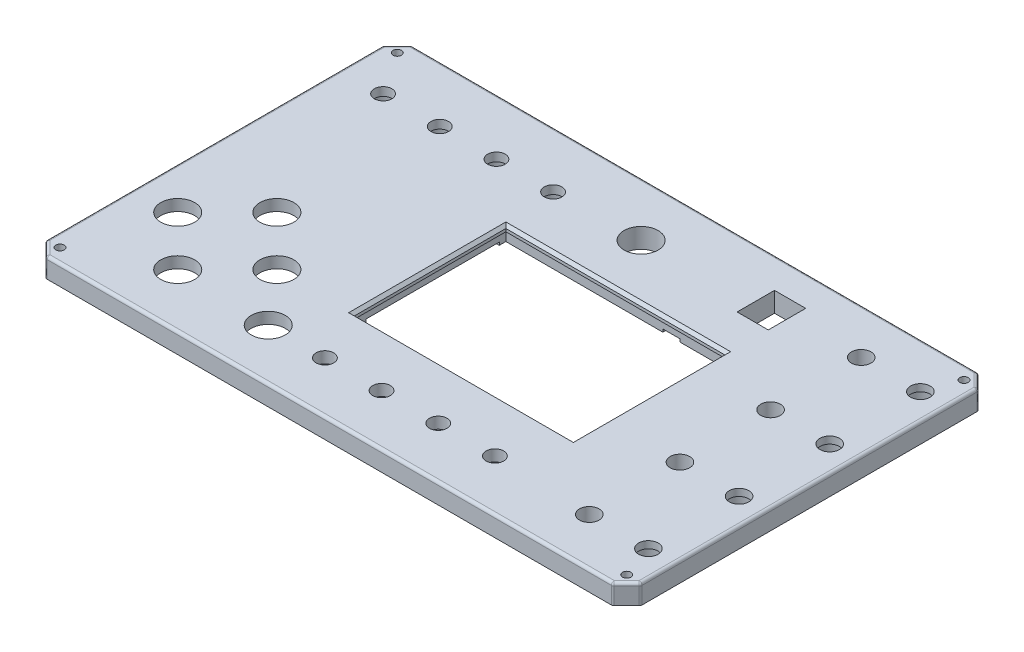
SolidWorks part; units mm, degrees
ref_plane "Front Plane" through (0, 0, 0) normal (0, 0, 1) x (1, 0, 0)
ref_plane "Top Plane" through (0, 0, 0) normal (0, 1, 0) x (1, 0, 0)
ref_plane "Right Plane" through (0, 0, 0) normal (1, 0, 0) x (0, 0, -1)
sketch "Sketch1" plane through (0, 0, 0) normal (0, 1, 0) x (1, 0, 0)
  line L1 (52.5, -34.5) -> (-52.5, -34.5)
  line L2 (52.5, -34.5) -> (52.5, 34.5)
  line L3 (52.5, 34.5) -> (-52.5, 34.5)
  line L4 (-52.5, -34.5) -> (-52.5, 34.5)
  line L5 (52.5, -34.5) -> (-52.5, 34.5) construction
  line L6 (52.5, 34.5) -> (-52.5, -34.5) construction
  point P0 (0, 0)
  dimension "D1" = 105
  dimension "D2" = 69
extrude "Boss-Extrude1" add sketch "Sketch1" along normal blind 5
extrude "Cut-Extrude1" cut sketch "Sketch2" against normal through all
sketch "Sketch2" plane through (17.0721, 0, 5.1034) normal (0, -1, 0) x (-1, 0, 0)
  line L0 (59.7281, 33.0909) -> (-27.1079, 33.0909)
  line L1 (-27.1079, 33.0909) -> (-27.1079, -24.4081)
  line L2 (-27.1079, -24.4081) -> (59.7281, -24.4081)
  line L3 (59.7281, -24.4081) -> (59.7281, 33.0909)
  line L8 (-26.1079, -23.4081) -> (58.7281, -23.4081) construction
  line L9 (-26.1079, 32.0909) -> (-26.1079, -23.4081) construction
  line L10 (58.7281, 32.0909) -> (-26.1079, 32.0909) construction
  line L11 (58.7281, -23.4081) -> (58.7281, 32.0909) construction
extrude "Cut-Extrude2" cut sketch "Sketch3" against normal blind 1
sketch "Sketch3" plane through (17.0721, 0, 5.1034) normal (0, -1, 0) x (-1, 0, 0)
  line L1 (59.8221, 30.7659) -> (54.5248, 30.7659)
  line L2 (59.8221, 30.7659) -> (59.8221, -16.2341) construction
  line L3 (59.8221, -16.2341) -> (54.5248, -16.2341)
  line L8 (65.3221, 30.2659) -> (60.3221, 30.2659) construction
  line L9 (60.3221, 30.2659) -> (60.3221, -15.7341) construction
  line L10 (60.3221, -15.7341) -> (65.3221, -15.7341) construction
  line L11 (65.3221, -15.7341) -> (65.3221, 30.2659) construction
  line L12 (54.5248, 30.7659) -> (54.5248, -16.2341)
  line L20 (65.8221, 30.7659) -> (59.8221, 30.7659)
  line L21 (59.8221, 30.7659) -> (59.8221, -16.2341) construction
  line L22 (59.8221, -16.2341) -> (65.8221, -16.2341)
  line L23 (65.8221, -16.2341) -> (65.8221, 30.7659)
extrude "Cut-Extrude3" cut sketch "Sketch4" against normal blind 1 contours L31 L28 L29 L17 L16 L19 | L19 L16 L17 | L30 L31 L19 L18 L17 L29 | L18 L19 L17 region at (15.76, 0, -28.9025) region at (12.8295, 0, -28.9025)
sketch "Sketch4" plane through (17.0721, 0, 5.1034) normal (0, -1, 0) x (-1, 0, 0)
  line L8 (69.5721, -29.3966) -> (69.5721, 69.6034)
  line L10 (-35.4279, 69.6034) -> (-35.4279, -29.3966)
  line L11 (-35.4279, -29.3966) -> (69.5721, -29.3966)
  line L16 (3.8121, 35.2559) -> (-1.1879, 35.2559)
  line L17 (-1.1879, 35.2559) -> (-1.1879, 32.7559)
  line L18 (-1.1879, 32.7559) -> (3.8121, 32.7559)
  line L19 (3.8121, 32.7559) -> (3.8121, 35.2559)
  line L20 (69.5721, 69.6034) -> (-35.4279, 69.6034)
  line L28 (4.3121, 35.7559) -> (-1.6879, 35.7559)
  line L29 (-1.6879, 35.7559) -> (-1.6879, 32.2559)
  line L30 (-1.6879, 32.2559) -> (4.3121, 32.2559)
  line L31 (4.3121, 32.2559) -> (4.3121, 35.7559)
extrude "Cut-Extrude4" cut sketch "Sketch5" against normal through all contours L3 L2 A3 L5 A2 L4 | L2 L3 L4 A4 L6 A5 region at (42.0883, 0, 0.4104)
sketch "Sketch5" plane through (17.0721, 0, 5.1034) normal (0, -1, 0) x (-1, 0, 0)
  line L2 (-27.1779, 33.1034) -> (-27.1779, 13.8376)
  line L3 (-27.1779, 5.1034) -> (-31.6779, 5.1034) construction
  line L4 (-31.6779, -0.8966) -> (-31.6779, 11.1034)
  line L5 (-30.1159, 12.6653) -> (-28.3501, 12.6653)
  line L6 (-29.4785, -3.0961) -> (-28.6478, -3.0961)
  line L7 (-27.1779, 5.1034) -> (-27.1779, 13.8376) construction
  line L8 (-27.1779, -4.566) -> (-18.8659, -4.566)
  line L9 (-27.1779, -4.566) -> (-27.1779, 5.1034)
  line L10 (-27.1779, 13.8376) -> (-18.8659, 13.8376)
  line L11 (-18.8659, -4.566) -> (-18.8659, 13.8376)
  line L12 (-27.1779, 13.8376) -> (-27.1779, 5.1034) construction
  line L13 (-27.1779, 5.1034) -> (-27.1779, -22.8966)
  arc A2 (-31.6779, 11.1034) -> (-30.1159, 12.6653) centre (-30.1159, 11.1034) cw
  arc A3 (-28.3501, 12.6653) -> (-27.1779, 13.8376) centre (-28.3501, 13.8376) ccw
  arc A4 (-31.6779, -0.8966) -> (-29.4785, -3.0961) centre (-29.4785, -0.8966) ccw
  arc A5 (-28.6478, -3.0961) -> (-27.1779, -4.566) centre (-28.6478, -4.566) cw
  point P8 (-31.6779, 5.1034)
extrude "Cut-Extrude7" cut sketch "Sketch9" against normal blind 4
sketch "Sketch9" plane through (17.0721, 0, 5.1034) normal (0, -1, 0) x (-1, 0, 0)
  circle A4 centre (-28.6779, -22.8966) radius 1.5 construction
  circle A5 centre (62.8221, -22.8966) radius 1.5 construction
  circle A6 centre (62.8221, 33.1034) radius 1.5 construction
  circle A7 centre (-28.6779, 33.1034) radius 1.5 construction
  circle A8 centre (-28.6779, 33.1034) radius 1
  circle A9 centre (62.8221, 33.1034) radius 1
  circle A10 centre (-28.6779, -22.8966) radius 1
  circle A11 centre (62.8221, -22.8966) radius 1
sketch "Sketch7" plane through (0, 5, 0) normal (0, 1, 0) x (1, 0, 0)
  line L1 (52.5, 34.5) -> (-52.5, 34.5)
  line L2 (52.5, 34.5) -> (52.5, 64.5)
  line L3 (52.5, 64.5) -> (-52.5, 64.5)
  line L4 (-52.5, 34.5) -> (-52.5, 64.5)
  line L5 (-52.5, -34.5) -> (52.5, -34.5)
  line L6 (-52.5, -34.5) -> (-52.5, -64.5)
  line L7 (-52.5, -64.5) -> (52.5, -64.5)
  line L8 (52.5, -34.5) -> (52.5, -64.5)
  line M17 (-52.5, -34.5) -> (52.5, -34.5)
  dimension "D1" = 30
  dimension "D2" = 30
extrude "Boss-Extrude2" add sketch "Sketch7" against normal up to surface (5 mm away) contours L8 L5 L7 M17 | L1 L4 L3 L2 region at (0, 5, 49.5) up to face at (-45.75, 0, -29)
sketch "Sketch8" plane through (0, 5, 0) normal (0, 1, 0) x (1, 0, 0)
  line L0 (52.5, 29.2726) -> (52.5, 64.5) construction
  line L1 (52.5, -64.5) -> (52.5, 64.5) construction
  line L2 (52.5, 46.8863) -> (26.68, 46.8863) construction
  line L3 (-52.5, 64.5) -> (-52.5, -64.5) construction
  line L4 (19.635, 46.8863) -> (19.635, 53.4863) construction
  line L5 (37.68, 40.2863) -> (26.68, 40.2863)
  line L6 (37.68, 40.2863) -> (37.68, 53.4863)
  line L7 (37.68, 53.4863) -> (26.68, 53.4863)
  line L8 (26.68, 40.2863) -> (26.68, 53.4863)
  line L9 (37.68, 40.2863) -> (26.68, 53.4863) construction
  line L10 (37.68, 53.4863) -> (26.68, 40.2863) construction
  line L11 (19.635, 40.2863) -> (8.635, 40.2863) construction
  line L12 (8.635, 40.2863) -> (8.635, 46.8863) construction
  line L13 (19.635, 53.4863) -> (8.635, 53.4863) construction
  line L14 (1.59, 46.8863) -> (1.59, 53.4863) construction
  line L15 (1.59, 40.2863) -> (-9.41, 40.2863) construction
  line L16 (-9.41, 46.8863) -> (-9.41, 53.4863) construction
  line L17 (1.59, 53.4863) -> (-9.41, 53.4863) construction
  line L18 (-16.455, 40.2863) -> (-16.455, 46.8863) construction
  line L19 (-16.455, 40.2863) -> (-27.455, 40.2863) construction
  line L20 (-27.455, 40.2863) -> (-27.455, 46.8863) construction
  line L21 (-16.455, 53.4863) -> (-27.455, 53.4863) construction
  line L22 (-34.5, 40.2863) -> (-34.5, 46.8863) construction
  line L23 (-34.5, 40.2863) -> (-45.5, 40.2863) construction
  line L24 (-45.5, 40.2863) -> (-45.5, 46.8863) construction
  line L25 (-34.5, 53.4863) -> (-45.5, 53.4863) construction
  line L26 (-45.5, 46.8863) -> (-45.5, 53.4863) construction
  line L27 (-34.5, 46.8863) -> (-34.5, 53.4863) construction
  line L28 (-27.455, 46.8863) -> (-34.5, 46.8863) construction
  line L29 (-34.5, 46.8863) -> (-52.5, 46.8863) construction
  line L30 (-16.455, 46.8863) -> (-27.455, 46.8863) construction
  line L31 (-27.455, 46.8863) -> (-27.455, 53.4863) construction
  line L32 (-16.455, 46.8863) -> (-16.455, 53.4863) construction
  line L33 (1.59, 40.2863) -> (1.59, 46.8863) construction
  line L34 (-9.41, 40.2863) -> (-9.41, 46.8863) construction
  line L35 (-9.41, 46.8863) -> (-16.455, 46.8863) construction
  line L36 (8.635, 46.8863) -> (8.635, 53.4863) construction
  line L37 (8.635, 46.8863) -> (1.59, 46.8863) construction
  line L38 (1.59, 46.8863) -> (-9.41, 46.8863) construction
  line L39 (19.635, 40.2863) -> (19.635, 46.8863) construction
  line L40 (26.68, 46.8863) -> (19.635, 46.8863) construction
  line L41 (19.635, 46.8863) -> (8.635, 46.8863) construction
  point P9 (32.18, 46.8863)
  point P14 (-40, 53.4863)
  dimension "D1" = 13.2
  dimension "D2" = 11
  dimension "D3" = 20.32
  dimension "D5" = 12.5
  dimension "D6" = 11
  dimension "D4" = 5
extrude "Cut-Extrude6" cut sketch "Sketch8" against normal through all
sketch "Sketch10" plane through (0, 5, 0) normal (0, 1, 0) x (1, 0, 0)
  line L0 (44.18, 27.9875) -> (44.18, 8.7342) construction
  line L1 (-52.5, 64.5) -> (52.5, 64.5)
  line L2 (-52.5, 64.5) -> (-52.5, -34.5)
  line L3 (-52.5, -34.5) -> (52.5, -34.5) construction
  line L4 (52.5, 64.5) -> (52.5, -34.5)
  line L5 (44.18, -9.6693) -> (44.18, -29.5115) construction
  line L6 (44.18, -29.5115) -> (-42.656, -29.5115) construction
  line L7 (-42.656, -29.5115) -> (-42.656, 27.9875) construction
  line L8 (-42.656, 27.9875) -> (44.18, 27.9875) construction
  line L9 (37.68, 40.2863) -> (37.68, 53.4863) construction
  line L10 (26.68, 40.2863) -> (37.68, 40.2863) construction
  line L11 (37.68, 53.4863) -> (26.68, 53.4863) construction
  line L12 (26.68, 53.4863) -> (26.68, 40.2863) construction
  line L29 (44.18, 27.9875) -> (44.18, 8.7342)
  line L30 (44.18, -9.6693) -> (44.18, -29.5115)
  line L31 (44.18, -29.5115) -> (-42.656, -29.5115)
  line L32 (-42.656, -29.5115) -> (-42.656, 27.9875)
  line L33 (-42.656, 27.9875) -> (44.18, 27.9875)
  line L34 (37.68, 40.2863) -> (37.68, 53.4863)
  line L35 (26.68, 40.2863) -> (37.68, 40.2863)
  line L36 (37.68, 53.4863) -> (26.68, 53.4863)
  line L37 (26.68, 53.4863) -> (26.68, 40.2863)
  line L54 (44.18, -9.6693) -> (44.18, 8.7342)
  line L59 (-52.5, 64.5) -> (-52.5, -64.5)
  line L60 (-52.5, -64.5) -> (52.5, -64.5)
  line L61 (52.5, -64.5) -> (52.5, 64.5)
  line L62 (52.5, 64.5) -> (-52.5, 64.5)
  line L63 (-52.5, 64.5) -> (-52.5, -64.5)
  line L64 (-52.5, -64.5) -> (52.5, -64.5)
  line L65 (52.5, -64.5) -> (52.5, 64.5)
  line L66 (52.5, 64.5) -> (-52.5, 64.5)
  line M11 (26.68, 40.2863) -> (26.68, 53.4863)
  line M12 (26.68, 53.4863) -> (37.68, 53.4863)
  line M13 (37.68, 53.4863) -> (37.68, 40.2863)
  line M14 (37.68, 40.2863) -> (26.68, 40.2863)
  line M31 (44.18, 27.9875) -> (44.18, 8.7342)
  line M32 (44.18, 8.7342) -> (44.25, 8.7342)
  arc M33 (44.25, 8.7342) -> (45.4223, 7.562) centre (45.4223, 8.7342) ccw
  line M34 (45.4223, 7.562) -> (47.188, 7.562)
  arc M35 (47.188, 7.562) -> (48.75, 6) centre (47.188, 6) cw
  line M36 (48.75, 6) -> (48.75, -6)
  arc M37 (48.75, -6) -> (46.5506, -8.1994) centre (46.5506, -6) cw
  line M38 (46.5506, -8.1994) -> (45.7199, -8.1994)
  arc M39 (45.7199, -8.1994) -> (44.25, -9.6693) centre (45.7199, -9.6693) ccw
  line M40 (44.25, -9.6693) -> (44.18, -9.6693)
  line M41 (44.18, -9.6693) -> (44.18, -29.5115)
  line M42 (44.18, -29.5115) -> (-42.656, -29.5115)
  line M43 (-42.656, -29.5115) -> (-42.656, 27.9875)
  line M44 (-42.656, 27.9875) -> (44.18, 27.9875)
  line M45 (-52.5, 64.5) -> (-52.5, -64.5)
  line M47 (52.5, -64.5) -> (52.5, 64.5)
  line M48 (52.5, 64.5) -> (-52.5, 64.5)
  line M70 (-52.5, -64.5) -> (52.5, -64.5)
  dimension "D1" = 0
extrude "Boss-Extrude3" add sketch "Sketch10" along normal blind 2 contours L3 M45 M47 M48 M44 M31 M32 M33 M34 M35 M36 M37 M38 M39 M40 M41 M42 M43 M14 M11 M12 M13 | L3 M45 M70 M47 | L54 M40 M39 M38 M37 M36 M35 M34 M33 M32 region at (-2.2738, 5, -29.4948) region at (0, 5, 49.5) region at (46.3986, 5, 0.2889)
sketch "Sketch11" plane through (0, 7, 0) normal (0, 1, 0) x (1, 0, 0)
  line L4 (-42.656, 27.9875) -> (-42.656, -29.5115)
  line L5 (44.18, 27.9875) -> (-42.656, 27.9875)
  line L6 (-42.656, -29.5115) -> (44.18, -29.5115)
  line L7 (44.18, -29.5115) -> (44.18, 27.9875)
  line L8 (36.68, -29.5115) -> (36.68, -27.5115) construction
  line L9 (44.18, -29.5115) -> (36.68, -29.5115)
  line L10 (44.18, -29.5115) -> (44.18, 27.9875)
  line L11 (44.18, 27.9875) -> (36.68, 27.9875)
  line L12 (36.68, -27.5115) -> (36.68, 25.9875)
  line L13 (-42.656, -29.5115) -> (36.68, -29.5115)
  line L14 (-42.656, -29.5115) -> (-42.656, -27.5115)
  line L15 (-40.656, -27.5115) -> (36.68, -27.5115)
  line L16 (36.68, -29.5115) -> (36.68, -27.5115) construction
  line L17 (-42.656, 27.9875) -> (36.68, 27.9875)
  line L18 (-42.656, 27.9875) -> (-42.656, 25.9875)
  line L19 (-40.656, 25.9875) -> (36.68, 25.9875)
  line L20 (36.68, 27.9875) -> (36.68, 25.9875) construction
  line L21 (-42.656, 27.9875) -> (-40.656, 27.9875)
  line L22 (-42.656, 27.9875) -> (-42.656, -29.5115)
  line L23 (-42.656, -29.5115) -> (-40.656, -29.5115)
  line L24 (-40.656, 25.9875) -> (-40.656, -27.5115)
  line L25 (-40.656, -27.5115) -> (-40.656, -29.5115) construction
  line L26 (-42.656, -27.5115) -> (-40.656, -27.5115) construction
  line L27 (-42.656, 25.9875) -> (-40.656, 25.9875) construction
  line L28 (-40.656, 27.9875) -> (-40.656, 25.9875) construction
  line L29 (36.68, 25.9875) -> (36.68, 27.9875) construction
  dimension "D1" = 7.5
  dimension "D2" = 2
  dimension "D3" = 2
  dimension "D4" = 2
extrude "Boss-Extrude4" add sketch "Sketch11" against normal blind 2 contours L13 L6 L5 L17 L4 L24 L19 L12 L15 region at (-41.656, 7, -26.946)
chamfer "Chamfer1" distance 1 angle 45 4 edges at (-1.988, 7, -25.9875) (-40.656, 7, 0.762) (-1.988, 7, 27.5115) (36.68, 7, 0.762)
sketch "Sketch12" plane through (0, 7, 0) normal (0, 1, 0) x (1, 0, 0)
  line L0 (-52.5, -64.5) -> (52.5, -64.5) construction
  line L1 (-52.5, -64.5) -> (-117.5, -64.5)
  line L2 (-52.5, -64.5) -> (-52.5, 64.5)
  line L3 (-52.5, 64.5) -> (-117.5, 64.5)
  line L4 (-117.5, -64.5) -> (-117.5, 64.5)
  line L5 (52.5, -64.5) -> (117.5, -64.5)
  line L6 (52.5, -64.5) -> (52.5, 64.5)
  line L7 (52.5, 64.5) -> (117.5, 64.5)
  line L8 (117.5, -64.5) -> (117.5, 64.5)
  line L9 (52.5, 64.5) -> (-52.5, 64.5) construction
  line L10 (-67.5, -28) -> (-102.5, -28) construction
  line L11 (-85, -45.5) -> (-85, -10.5) construction
  circle A0 centre (-85, -10.5) radius 6
  circle A1 centre (-85, -45.5) radius 6
  circle A2 centre (-102.5, -28) radius 6
  circle A3 centre (-67.5, -28) radius 6
  circle A4 centre (-85, -10.5) radius 8.5 construction
  circle A5 centre (-102.5, -28) radius 8.5 construction
  circle A6 centre (-67.5, -28) radius 8.5 construction
  circle A7 centre (-85, -45.5) radius 8.5 construction
  point P4 (-85, 64.5)
  point P19 (-85, -28)
  line M72 (-52.5, 64.5) -> (-52.5, -64.5)
  dimension "D3" = 12
  dimension "D7" = 17
  dimension "D8" = 17
  dimension "D1" = 65
  dimension "D2" = 65
  dimension "D4" = 35
  dimension "D5" = 75
  dimension "D6" = 35
extrude "Boss-Extrude5" add sketch "Sketch12" against normal up to surface (7 mm away) contours L4 L1 L3 M72 region at (-85, 7, -1.5968) up to face at (32.18, 0, -46.8863)
sketch "Sketch15" plane through (0, 7, 0) normal (0, 1, 0) x (1, 0, 0)
  line L0 (-117.5, -64.5) -> (52.5, -64.5) construction
  line L1 (-41.656, -28.5115) -> (37.68, -28.5115)
  line L2 (-41.656, -28.5115) -> (-41.656, -64.5)
  line L3 (-41.656, -64.5) -> (37.68, -64.5)
  line L4 (37.68, -28.5115) -> (37.68, -64.5)
  line L5 (-41.656, -46.5057) -> (37.68, -46.5057) construction
  circle A0 centre (-32.041, -46.5057) radius 3.1
  circle A1 centre (-12.041, -46.5057) radius 3.1
  circle A2 centre (7.959, -46.5057) radius 3.1
  circle A3 centre (27.959, -46.5057) radius 3.1
  dimension "D1" = 6.2
  dimension "D2" = 9.615
  dimension "D3" = 4
extrude "Cut-Extrude8" cut sketch "Sketch15" against normal through all contours A0 L5 | A1 L5 | L5 A1 | L5 A0 | A2 L5 | L5 A2 | A3 L5 | L5 A3 | A1 region at (-32.041, 7, 45.1901) region at (-32.041, 7, 47.8214) region at (27.959, 7, 47.8214) region at (27.959, 7, 45.1901) region at (-12.041, 7, 45.1901) region at (-12.041, 7, 47.8214) region at (7.959, 7, 47.8214) region at (7.959, 7, 45.1901)
sketch "Sketch16" plane through (0, 0, 0) normal (0, -1, 0) x (1, 0, 0)
  circle A0 centre (27.959, 46.5057) radius 3.1 construction
  circle A1 centre (7.959, 46.5057) radius 3.1 construction
  circle A2 centre (-12.041, 46.5057) radius 3.1 construction
  circle A3 centre (-32.041, 46.5057) radius 3.1 construction
  circle A4 centre (27.959, 46.5057) radius 3.1
  circle A5 centre (7.959, 46.5057) radius 3.1
  circle A6 centre (-12.041, 46.5057) radius 3.1
  circle A7 centre (-32.041, 46.5057) radius 3.1
  circle A8 centre (-32.041, 46.5057) radius 5.5
  circle A9 centre (-12.041, 46.5057) radius 5.5
  circle A10 centre (7.959, 46.5057) radius 5.5
  circle A11 centre (27.959, 46.5057) radius 5.5
  dimension "D1" = 11
extrude "Cut-Extrude9" cut sketch "Sketch16" against normal blind 3
sketch "Sketch18" plane through (0, 0, 0) normal (0, -1, 0) x (1, 0, 0)
  circle A0 centre (-85, 45.5) radius 10
  circle A1 centre (-102.5, 28) radius 10
  circle A2 centre (-85, 10.5) radius 10
  circle A3 centre (-67.5, 28) radius 10
  dimension "D1" = 20
extrude "Cut-Extrude10" cut sketch "Sketch18" against normal blind 3
chamfer "Chamfer2" distance 1 angle 45 4 edges at (-85, 0, 0.5) (-67.5, 0, 18) (-102.5, 0, 18) (-85, 0, 35.5)
sketch "Sketch19" plane through (0, 0, 0) normal (0, -1, 0) x (1, 0, 0)
  line L0 (-117.5, -64.5) -> (52.5, -64.5) construction
  line L1 (-42.656, -27.9875) -> (26.68, -27.9875)
  line L2 (-42.656, -27.9875) -> (-42.656, -64.5)
  line L4 (26.68, -27.9875) -> (26.68, -64.5)
  line L5 (26.68, -64.5) -> (-7.988, -64.5) construction
  line L6 (26.68, -64.5) -> (-7.988, -64.5) construction
  line L7 (18.196, -64.5) -> (0.496, -64.5)
  line L8 (18.196, -64.5) -> (18.196, -51)
  line L9 (18.196, -51) -> (0.496, -51)
  line L10 (0.496, -64.5) -> (0.496, -51)
  point P12 (9.346, -64.5)
  point P13 (9.346, -64.5)
  line M50 (-117.5, -64.5) -> (52.5, -64.5)
  dimension "D1" = 17.7
  dimension "D2" = 13.5
extrude "Cut-Extrude11" cut sketch "Sketch19" against normal blind 2 contours L10 L8 L9 M50 region at (9.346, 0, -57.75)
sketch "Sketch20" plane through (0, 2, 0) normal (0, -1, 0) x (1, 0, 0)
  line L0 (5.496, -62.5) -> (10.696, -62.5) construction
  line L1 (5.496, -61.0866) -> (10.696, -61.0866)
  line L3 (18.196, -64.5) -> (18.196, -51) construction
  line L4 (0.496, -64.5) -> (0.496, -51) construction
  line L5 (0.496, -64.5) -> (18.196, -64.5) construction
  line L6 (18.196, -64.5) -> (18.196, -51) construction
  line L7 (0.496, -64.5) -> (18.196, -64.5)
  line L8 (0.496, -64.5) -> (0.496, -61.0866)
  line L9 (0.496, -61.0866) -> (18.196, -61.0866)
  line L10 (18.196, -64.5) -> (18.196, -61.0866)
  line L12 (0.496, -51) -> (18.196, -51)
  line L13 (0.496, -51) -> (0.496, -55.2225)
  line L14 (0.496, -55.2225) -> (18.196, -55.2225)
  line L15 (18.196, -51) -> (18.196, -55.2225)
  point P2 (8.096, -62.5)
  line M2 (0.496, -51) -> (0.496, -64.5)
  line M4 (18.196, -64.5) -> (18.196, -51)
  line M5 (18.196, -51) -> (0.496, -51)
  dimension "D1" = 7.5
  dimension "D2" = 5
  dimension "D3" = 2
extrude "Cut-Extrude12" cut sketch "Sketch20" against normal blind 1 contours L10 L9 L1 | L14 M2 M4 M5 region at (9.346, 2, -62.7933) region at (9.346, 2, -53.1112)
sketch "Sketch22" plane through (0, 0, 0) normal (0, -1, 0) x (1, 0, 0)
  line L0 (-117.5, -64.5) -> (0.496, -64.5) construction
  line L1 (-24.8391, -64.5) -> (-60.3391, -64.5)
  line L2 (-24.8391, -64.5) -> (-24.8391, -54.5)
  line L3 (-24.8391, -54.5) -> (-60.3391, -54.5)
  line L4 (-60.3391, -64.5) -> (-60.3391, -54.5)
  circle A0 centre (-57.8391, -59.5) radius 1
  dimension "D4" = 2
  dimension "D1" = 10
  dimension "D2" = 35.5
  dimension "D3" = 2.5
extrude "Cut-Extrude13" cut sketch "Sketch22" against normal blind 2
sketch "Sketch23" plane through (0, 0, 0) normal (0, -1, 0) x (1, 0, 0)
  circle A1 centre (-57.8391, -59.5) radius 1
  circle A2 centre (-57.8391, -59.5) radius 1
  dimension "D1" = 0
extrude "Cut-Extrude14" cut sketch "Sketch23" against normal blind 4
sketch "Sketch24" plane through (0, 2, 0) normal (0, -1, 0) x (1, 0, 0)
  line L0 (-35.8391, -63) -> (-25.8391, -63) construction
  line L1 (-35.8391, -62.0036) -> (-25.8391, -62.0036)
  line L2 (-35.8391, -63.9964) -> (-25.8391, -63.9964)
  line L3 (-60.3391, -64.5) -> (-24.8391, -64.5) construction
  line L4 (-24.8391, -64.5) -> (-24.8391, -54.5) construction
  arc A0 (-35.8391, -62.0036) -> (-35.8391, -63.9964) centre (-35.8391, -63) ccw
  arc A1 (-25.8391, -63.9964) -> (-25.8391, -62.0036) centre (-25.8391, -63) ccw
  point P2 (-30.8391, -63)
  dimension "D1" = 1.5
  dimension "D2" = 6
  dimension "D3" = 10
extrude "Cut-Extrude15" cut sketch "Sketch24" against normal blind 1
sketch "Sketch25" plane through (0, 7, 0) normal (0, 1, 0) x (1, 0, 0)
  line L0 (52.5, 64.5) -> (-117.5, 64.5) construction
  line L1 (-117.5, -64.5) -> (-117.5, 64.5) construction
  circle A0 centre (-102.5, 44.5) radius 3.1
  circle A1 centre (-82.5, 44.5) radius 3.1
  dimension "D1" = 6.2
  dimension "D2" = 20
  dimension "D3" = 20
  dimension "D4" = 15
extrude "Cut-Extrude16" cut sketch "Sketch25" against normal through all
sketch "Sketch26" plane through (0, 0, 0) normal (0, -1, 0) x (1, 0, 0)
  circle A0 centre (-102.5, -44.5) radius 5.15
  circle A1 centre (-82.5, -44.5) radius 5.15
  dimension "D1" = 10.3
extrude "Cut-Extrude17" cut sketch "Sketch26" against normal blind 4
sketch "Sketch27" plane through (0, 7, 0) normal (0, 1, 0) x (1, 0, 0)
  line L1 (52.5, 64.5) -> (92.5, 64.5)
  line L2 (52.5, 64.5) -> (52.5, -64.5)
  line L3 (52.5, -64.5) -> (92.5, -64.5)
  line L4 (92.5, 64.5) -> (92.5, -64.5)
  dimension "D1" = 40
extrude "Boss-Extrude6" add sketch "Sketch27" against normal up to surface (7 mm away) up to face at (-102.5, 0, -49.65)
pattern_linear "LPattern1" count 2 spacing 40 along (1, 0, 0) of "Cut-Extrude17", "Cut-Extrude16"
sketch "Sketch28" plane through (0, 7, 0) normal (0, 1, 0) x (1, 0, 0)
  line L0 (37.68, -0.762) -> (92.5, 0) construction
  line L1 (37.68, 26.9875) -> (37.68, -28.5115) construction
  line L2 (92.5, -64.5) -> (92.5, 64.5) construction
  line L3 (37.68, -0.762) -> (65.09, -0.381)
  line L4 (92.5, 64.5) -> (-117.5, 64.5) construction
  line L6 (65.09, -0.381) -> (65.09, -64.5) construction
  line L7 (-117.5, -64.5) -> (92.5, -64.5) construction
  line L8 (72.5, 32.0595) -> (72.5, 64.5) construction
  circle A0 centre (62.5, 48.2798) radius 3.45
  circle A1 centre (62.5, 48.2798) radius 11.75 construction
  circle A2 centre (62.5, 16.2798) radius 3.45
  circle A3 centre (62.5, 16.2798) radius 11.75 construction
  circle A4 centre (62.5, -15.7202) radius 3.45
  circle A5 centre (62.5, -15.7202) radius 11.75 construction
  circle A6 centre (62.5, -47.7202) radius 3.45
  circle A7 centre (62.5, -47.7202) radius 11.75 construction
  point P17 (72.5, 48.2798)
  dimension "D2" = 6.9
  dimension "D3" = 30
  dimension "D1" = 4
extrude "Cut-Extrude18" cut sketch "Sketch28" against normal through all contours A0 | A2 | A4 | A6 region at (62.5, 7, -48.2798) region at (62.5, 7, -16.2798) region at (62.5, 7, 15.7202) region at (62.5, 7, 47.7202)
sketch "Sketch29" plane through (0, 7, 0) normal (0, 1, 0) x (1, 0, 0)
  line L0 (74.25, 48.2798) -> (92.5, 48.2798) construction
  line L1 (92.5, -64.5) -> (92.5, 64.5) construction
  circle A0 centre (62.5, 48.2798) radius 11.75 construction
  circle A1 centre (83.375, 48.2798) radius 3.45
  circle A2 centre (83.375, 16.2798) radius 3.45
  circle A3 centre (83.375, -15.7202) radius 3.45
  circle A4 centre (83.375, -47.7202) radius 3.45
  dimension "D1" = 6.9
  dimension "D2" = 4
extrude "Cut-Extrude19" cut sketch "Sketch29" against normal through all
sketch "Sketch30" plane through (0, 0, 0) normal (0, -1, 0) x (1, 0, 0)
  circle A0 centre (83.375, -48.2798) radius 5
  circle A1 centre (83.375, -16.2798) radius 5
  circle A2 centre (83.375, 15.7202) radius 5
  circle A3 centre (83.375, 47.7202) radius 5
  dimension "D1" = 10
  dimension "D2" = 4
extrude "Cut-Extrude20" cut sketch "Sketch30" against normal blind 4.5
sketch "Sketch31" plane through (0, 0, 0) normal (0, -1, 0) x (1, 0, 0)
  circle A0 centre (62.5, 47.7202) radius 5.5
  circle A1 centre (62.5, 15.7202) radius 5.5
  circle A2 centre (62.5, -16.2798) radius 5.5
  circle A3 centre (62.5, -48.2798) radius 5.5
  dimension "D1" = 11
  dimension "D2" = 4
extrude "Cut-Extrude21" cut sketch "Sketch31" against normal blind 2
sketch "Sketch32" plane through (0, 0, 0) normal (0, -1, 0) x (1, 0, 0)
  line L0 (69.9505, 49.2202) -> (70.9682, 49.2202)
  line L2 (61, 56.1884) -> (61, 55.1708)
  line L4 (64, 56.1884) -> (64, 55.1708)
  line L5 (54.0318, 49.2202) -> (55.0495, 49.2202)
  line L7 (54.0318, 46.2202) -> (55.0495, 46.2202)
  line L9 (69.9505, 46.2202) -> (70.9682, 46.2202)
  line L12 (64, 40.2697) -> (64, 39.2521)
  line L13 (61, 40.2697) -> (61, 39.2521)
  arc A0 (54.0318, 49.2202) -> (54.0318, 46.2202) centre (62.5, 47.7202) ccw
  arc A1 (55.0495, 49.2202) -> (55.0495, 46.2202) centre (62.5, 47.7202) ccw
  circle A2 centre (62.5, 47.7202) radius 8.6 construction
  circle A3 centre (62.5, 47.7202) radius 7.6 construction
  arc A4 (64, 56.1884) -> (61, 56.1884) centre (62.5, 47.7202) ccw
  arc A5 (64, 55.1708) -> (61, 55.1708) centre (62.5, 47.7202) ccw
  arc A6 (70.9682, 46.2202) -> (70.9682, 49.2202) centre (62.5, 47.7202) ccw
  arc A7 (69.9505, 46.2202) -> (69.9505, 49.2202) centre (62.5, 47.7202) ccw
  arc A8 (61, 39.2521) -> (64, 39.2521) centre (62.5, 47.7202) ccw
  arc A9 (61, 40.2697) -> (64, 40.2697) centre (62.5, 47.7202) ccw
  dimension "D1" = 1
  dimension "17.2" = 17.2
  dimension "D3" = 3
extrude "Cut-Extrude22" cut sketch "Sketch32" against normal blind 2.5
pattern_linear "LPattern2" count 4 spacing 32 along (0, 0, -1) of "Cut-Extrude22"
sketch "Sketch33" plane through (0, 7, 0) normal (0, 1, 0) x (1, 0, 0)
  circle A0 centre (-52.041, -46.5057) radius 6
  circle A1 centre (-67.5, -28) radius 6 construction
  circle A2 centre (-32.041, -46.5057) radius 3.1 construction
  circle A3 centre (-67.5, -28) radius 6
  circle A4 centre (-32.041, -46.5057) radius 3.1
  dimension "D1" = 20
extrude "Cut-Extrude23" cut sketch "Sketch33" against normal through all contours A0 region at (-52.041, 7, 46.5057)
sketch "Sketch34" plane through (0, 0, 0) normal (0, -1, 0) x (1, 0, 0)
  circle A0 centre (-52.041, 46.5057) radius 10
  circle A1 centre (-67.5, 28) radius 10 construction
  circle A2 centre (-67.5, 28) radius 10
extrude "Cut-Extrude24" cut sketch "Sketch34" against normal up to surface (3 mm away) contours A0 region at (-52.041, 0, 46.5057) up to face at (-67.5, 3, 18)
chamfer "Chamfer3" distance 1 angle 45 1 edges at (-52.041, 0, 36.5057)
chamfer "Chamfer4" distance 5 angle 45 4 edges at (92.5, 3.5, -64.5) (92.5, 3.5, 64.5) (-117.5, 3.5, 64.5) (-117.5, 3.5, -64.5)
fillet "Fillet1" radius 1 16 edges at (87.5, 3.5, 64.5) (92.5, 3.5, 59.5) (-112.5, 3.5, 64.5) (-117.5, 3.5, 59.5) (-117.5, 3.5, -59.5) (-112.5, 3.5, -64.5) (90, 7, 62) (-12.5, 7, 64.5) (-115, 7, 62) (-117.5, 7, 0) (-115, 7, -62) (-12.5, 7, -64.5) (87.5, 3.5, -64.5) (92.5, 3.5, -59.5) (92.5, 7, 0) (90, 7, -62)
sketch "Sketch36" plane through (0, 0, 0) normal (0, -1, 0) x (1, 0, 0)
  line L8 (-115, 62) -> (-110.0537, 57.0537) construction
  line L9 (-112.7929, 64.2071) -> (-117.2071, 59.7929) construction
  line L10 (-115, -62) -> (-110.0503, -57.0503) construction
  line L11 (-117.2071, -59.7929) -> (-112.7929, -64.2071) construction
  line L12 (90, -62) -> (85.0503, -57.0503) construction
  line L13 (87.7929, -64.2071) -> (92.2071, -59.7929) construction
  line L14 (90, 62) -> (85.0503, 57.0503) construction
  line L15 (92.2071, 59.7929) -> (87.7929, 64.2071) construction
  circle A0 centre (-112.5268, 59.5268) radius 1.5
  circle A1 centre (-112.5251, -59.5251) radius 1.5
  circle A2 centre (87.5251, -59.5251) radius 1.5
  circle A3 centre (87.5251, 59.5251) radius 1.5
  dimension "D1" = 3
  dimension "D4" = 3
  dimension "D6" = 3
  dimension "D8" = 3
  dimension "D2" = 6.9952
  dimension "D3" = 7
  dimension "D5" = 7
  dimension "D7" = 7
extrude "Cut-Extrude25" cut sketch "Sketch36" against normal through all contours A3 | A2 | A1 | A0 | A3 region at (-112.5268, 0, 59.5268) region at (-112.5251, 0, -59.5251) region at (87.5251, 0, -59.5251) region at (87.5251, 0, 59.5251)
sketch "Sketch38" plane through (0, 0, 0) normal (0, -1, 0) x (1, 0, 0)
  line L0 (-117.5, -24.3675) -> (-48.75, -24.3675) construction
  line L2 (-48.75, 21.3375) -> (-48.75, -25.6625) construction
  line L3 (-117.5, -59.0858) -> (-117.5, 59.0858) construction
  text T0 "PROJECT TITAN\r\nJUST BETTER\r\n2025" font "ROG Fonts" height in points 16
extrude "Cut-Extrude27" cut sketch "Sketch38" against normal blind 2
sketch "Sketch39" plane through (0, 7, 0) normal (0, 1, 0) x (1, 0, 0)
  line L8 (-112.0858, -63.5) -> (87.0858, -63.5)
  line L9 (87.0858, -63.5) -> (91.5, -59.0858)
  line L10 (91.5, -59.0858) -> (91.5, 59.0858)
  line L11 (91.5, 59.0858) -> (87.0858, 63.5)
  line L12 (87.0858, 63.5) -> (-112.0858, 63.5)
  line L13 (-112.0858, 63.5) -> (-116.5, 59.0858)
  line L14 (-116.5, 59.0858) -> (-116.5, -59.0858)
  line L15 (-116.5, -59.0858) -> (-112.0858, -63.5)
  line L16 (-112.0858, -63.5) -> (87.0858, -63.5)
  line L17 (87.0858, -63.5) -> (91.5, -59.0858)
  line L18 (91.5, -59.0858) -> (91.5, 59.0858)
  line L19 (91.5, 59.0858) -> (87.0858, 63.5)
  line L20 (87.0858, 63.5) -> (-112.0858, 63.5)
  line L21 (-112.0858, 63.5) -> (-116.5, 59.0858)
  line L22 (-116.5, 59.0858) -> (-116.5, -59.0858)
  line L23 (-116.5, -59.0858) -> (-112.0858, -63.5)
  dimension "D1" = 0
sketch "Sketch40" plane through (0, 7, 0) normal (0, 1, 0) x (1, 0, 0)
  line L0 (-24.8391, 64.5) -> (-24.8391, 54.5) construction
  line L1 (0.496, 64.5) -> (0.496, 51) construction
  line L2 (-24.8391, 64.5) -> (-24.8391, 54.5)
  line L3 (0.496, 64.5) -> (0.496, 51)
  line L4 (-24.8391, 59.5) -> (0.496, 59.5) construction
  line L5 (0.496, 59.5) -> (-12.1715, 59.5) construction
  line L6 (-12.1715, 59.5) -> (-12.1715, 64.5) construction
  line L7 (-112.0858, 64.5) -> (87.0858, 64.5) construction
  line L8 (-12.1715, 64.5) -> (-12.1715, 25.9875) construction
  line L9 (36.68, 25.9875) -> (-40.656, 25.9875) construction
  line L11 (-4.1715, 30.2437) -> (-20.1715, 30.2437)
  line L12 (-4.1715, 30.2437) -> (-4.1715, 60.2437)
  line L13 (-4.1715, 60.2437) -> (-20.1715, 60.2437)
  line L14 (-20.1715, 30.2437) -> (-20.1715, 60.2437)
  line L15 (-4.1715, 30.2437) -> (-20.1715, 60.2437) construction
  line L16 (-4.1715, 60.2437) -> (-20.1715, 30.2437) construction
  circle A0 centre (-12.1715, 45.2437) radius 6
  dimension "D1" = 30
  dimension "D2" = 16
extrude "Cut-Extrude28" cut sketch "Sketch40" against normal through all contours A0 region at (-12.1715, 7, -45.2437)
